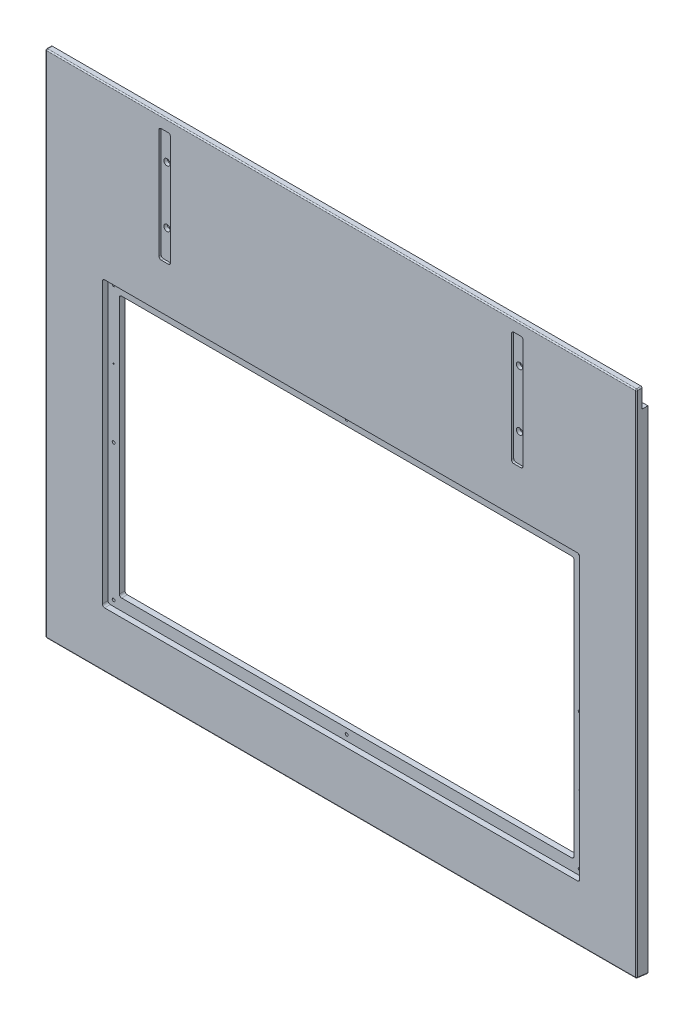
SolidWorks part; units mm, degrees
ref_plane "Front Plane" through (0, 0, 0) normal (0, 0, 1) x (1, 0, 0)
ref_plane "Top Plane" through (0, 0, 0) normal (0, 1, 0) x (1, 0, 0)
ref_plane "Right Plane" through (0, 0, 0) normal (1, 0, 0) x (0, 0, -1)
sketch "Sketch2" plane through (0, 0, 0) normal (0, 0, 1) x (1, 0, 0)
  line L1 (-260, -390) -> (260, -390)
  line L2 (-260, -390) -> (-260, 60)
  line L3 (-260, 60) -> (260, 60)
  line L4 (260, -390) -> (260, 60)
  line L5 (-260, -390) -> (260, 60) construction
  line L6 (-260, 60) -> (260, -390) construction
  point P0 (0, -165)
  dimension "D1" = 60
  dimension "D2" = 520
  dimension "D3" = 450
extrude "Boss-Extrude2" add sketch "Sketch2" against normal blind 10
ref_plane "Plane1" through (0, -215, 0) normal (0, 1, 0) x (1, 0, 0)
ref_axis "Axis1" through (0, -215, 0.5) along (0, 0, -1)
sketch "Sketch3" plane through (0, 0, 0) normal (0, 0, 1) x (1, 0, 0)
  line L1 (-160.2, 50.1) -> (-150, 50.1)
  line L2 (-160.2, 50.1) -> (-160.2, -50.1)
  line L3 (-160.2, -50.1) -> (-150, -50.1)
  line L4 (-150, 50.1) -> (-150, -50.1)
  line L5 (-160.2, 50.1) -> (-150, -50.1) construction
  line L6 (-160.2, -50.1) -> (-150, 50.1) construction
  line L7 (5.5, 0) -> (-5.5, 0) construction
  line L8 (0, -5.5) -> (0, 5.5) construction
  point P0 (-155.1, 0)
  dimension "D1" = 155.1
  dimension "D2" = 10.2
  dimension "D3" = 100.2
extrude "Cut-Extrude1" cut sketch "Sketch3" against normal blind 2
fillet "Fillet2" radius 2 4 edges at (-160.2, -50.1, -1) (-150, -50.1, -1) (-150, 50.1, -1) (-160.2, 50.1, -1)
hole_wizard "CBORE for M5 SHCS1" positions "Sketch5" profile "Sketch6" counterbore size "M5" standard "ANSI Metric" end condition through all
sketch "Sketch5" plane through (0, 0, -10) normal (0, 0, -1) x (-1, 0, 0)
  line L0 (5.5, 0) -> (-5.5, 0) construction
  line L2 (0, 5.5) -> (0, -5.5) construction
  point P0 (155.1, 25)
  point P3 (155.1, -25)
  dimension "D1" = 25
  dimension "D2" = 25
  dimension "D3" = 155.1
sketch "Sketch6" plane through (-155.1, 25, -10) normal (1, 0, 0) x (0, 1, 0)
  line L0 (0, 0) -> (0, 10)
  line L1 (0, 10) -> (2.75, 10)
  line L3 (2.75, 10) -> (2.75, 5)
  line L4 (2.75, 5) -> (5, 5)
  line L5 (5, 5) -> (5, 0)
  line L7 (5, 0) -> (0, 0)
  line L11 (0, -6.35) -> (0, 107.95) construction
  dimension "Thru Hole Dia." = 5.5
  dimension "Thru Hole Depth" = 10
  dimension "C'Bore Dia." = 10
  dimension "C'Bore Depth" = 5
mirror "Mirror8" about plane through (0, 0, 0) normal (1, 0, 0) of "CBORE for M5 SHCS1", "Fillet2", "Cut-Extrude1"
sketch "Sketch7" plane through (0, 0, 0) normal (0, 0, 1) x (1, 0, 0)
  line L1 (-200, -100) -> (200, -100)
  line L2 (-200, -100) -> (-200, -330)
  line L3 (-200, -330) -> (200, -330)
  line L4 (200, -100) -> (200, -330)
  line L5 (-200, -100) -> (200, -330) construction
  line L6 (-200, -330) -> (200, -100) construction
  point P0 (0, -215)
  dimension "D1" = 400
  dimension "D2" = 230
extrude "Cut-Extrude3" cut sketch "Sketch7" against normal through all
fillet "Fillet3" radius 2 4 edges at (200, -330, -5) (200, -100, -5) (-200, -330, -5) (-200, -100, -5)
sketch "Sketch9" plane through (0, 0, 0) normal (0, 0, 1) x (1, 0, 0)
  line L0 (-200, -102) -> (-200, -328) construction
  line L1 (-210, -90) -> (210, -90)
  line L2 (-210, -90) -> (-210, -340)
  line L3 (-210, -340) -> (210, -340)
  line L4 (210, -90) -> (210, -340)
  line L5 (-210, -90) -> (210, -340) construction
  line L6 (-210, -340) -> (210, -90) construction
  line L7 (-198, -330) -> (198, -330) construction
  point P0 (0, -215)
  dimension "D1" = 10
  dimension "D2" = 10
extrude "Cut-Extrude5" cut sketch "Sketch9" against normal blind 5
fillet "Fillet4" radius 2 4 edges at (210, -90, -2.5) (210, -340, -2.5) (-210, -340, -2.5) (-210, -90, -2.5)
hole_wizard "M3 Tapped Hole1" positions "Sketch13" profile "Sketch14" tap size "M3" standard "DIN" end condition through all
sketch "Sketch13" plane through (0, 0, -5) normal (0, 0, 1) x (1, 0, 0)
  line L0 (0, -5.5) -> (0, 5.5) construction
  line L1 (5.5, -215) -> (-5.5, -215) construction
  line L4 (-200, -328) -> (-200, -102) construction
  line L5 (-198, -100) -> (198, -100) construction
  line L6 (198, -330) -> (-198, -330) construction
  line L7 (200, -102) -> (200, -328) construction
  point P0 (-205, -95)
  point P2 (0, -95)
  point P4 (-205, -215)
  point P21 (205, -95)
  point P23 (205, -215)
  point P25 (205, -335)
  point P27 (0, -335)
  point P29 (-205, -335)
  dimension "D1" = 5
  dimension "D2" = 5
  dimension "D3" = 5
  dimension "D4" = 5
sketch "Sketch14" plane through (-205, -95, -5) normal (1, 0, 0) x (0, -1, 0)
  line L0 (0, 0) -> (0, 5)
  line L1 (0, 5) -> (1.25, 5)
  line L2 (1.25, 5) -> (1.25, 0)
  line L5 (1.25, 0) -> (0, 0)
  line L11 (0, -6.35) -> (0, 107.95) construction
  dimension "Thru Tap Drill Dia." = 2.5
  dimension "Thru Tap Drill Depth" = 5
cosmetic thread "Hole Thread1" parameters "D2"=3
cosmetic thread "Hole Thread2" parameters "D2"=3
cosmetic thread "Hole Thread3" parameters "D2"=3
cosmetic thread "Hole Thread4" parameters "D2"=3
cosmetic thread "Hole Thread5" parameters "D2"=3
cosmetic thread "Hole Thread6" parameters "D2"=3
cosmetic thread "Hole Thread7" parameters "D2"=3
cosmetic thread "Hole Thread8" parameters "D2"=3
sketch "Sketch12" plane through (0, 0, -10) normal (0, 0, -1) x (-1, 0, 0)
  line L0 (260, -390) -> (-260, -390) construction
  line L1 (10, -390) -> (-10, -390)
  line L2 (10, -390) -> (10, -386.5)
  line L3 (7.5, -384) -> (-7.5, -384)
  line L4 (-10, -390) -> (-10, -386.5)
  line L5 (10, -390) -> (-10, -384) construction
  line L6 (10, -384) -> (-10, -390) construction
  line L7 (0, 5.5) -> (0, -5.5) construction
  arc A0 (-7.5, -384) -> (-10, -386.5) centre (-7.5, -386.5) ccw
  arc A1 (10, -386.5) -> (7.5, -384) centre (7.5, -386.5) ccw
  point P0 (0, -387)
  dimension "D3" = 2.5
  dimension "D1" = 20
  dimension "D2" = 6
extrude "Cut-Extrude8" cut sketch "Sketch12" against normal blind 6
sketch "Sketch11" plane through (0, 0, 0) normal (1, 0, 0) x (0, 0, -1)
  line L0 (10, -390) -> (0, -388.6853)
  line L1 (10, 60) -> (5, 60)
  line L2 (10, 60) -> (10, 43)
  line L3 (10, 43) -> (5, 43)
  line L4 (5, 60) -> (5, 43)
  line L5 (0, 60) -> (0, -390) construction
  line L6 (0, -388.6853) -> (0, -390)
  line L7 (0, -390) -> (10, -390)
  dimension "D1" = 5
  dimension "D2" = 17
  dimension "D3" = 7.49
extrude "Cut-Extrude7" cut sketch "Sketch11" against normal through all both and the other way through all
fillet "Fillet1" radius 1 8 edges at (-260, 60, -2.5) (260, 60, -2.5) (260, -389.3426, -5) (-260, -389.3426, -5) (0, 60, 0) (-260, -164.3426, 0) (0, -388.6853, 0) (260, -164.3426, 0)
hole_wizard "M5x0.8 Tapped Hole1" positions "Sketch15" profile "Sketch16" tap size "M5x0.8" standard "ANSI Metric"
sketch "Sketch15" plane through (0, 0, -10) normal (0, 0, -1) x (-1, 0, 0)
  line L0 (0, 5.5) -> (0, -5.5) construction
  line L1 (259, 60) -> (-259, 60) construction
  point P0 (-215, 34)
  point P2 (-190, 34)
  point P4 (-12.5, 34)
  point P6 (12.5, 34)
  point P8 (190, 34)
  point P10 (215, 34)
  dimension "D1" = 12.5
  dimension "D2" = 12.5
  dimension "D3" = 25
  dimension "D4" = 25
  dimension "D5" = 190
  dimension "D6" = 190
  dimension "D7" = 26
sketch "Sketch16" plane through (215, 34, -10) normal (1, 0, 0) x (0, 1, 0)
  line L0 (0, 0) -> (0, 9.2618)
  line L1 (0, 9.2618) -> (2.1, 8)
  line L2 (2.1, 8) -> (2.1, 0)
  line L5 (2.1, 0) -> (0, 0)
  line L10 (0, 9.2618) -> (-2.1, 8) construction
  line L11 (0, -6.35) -> (0, 107.95) construction
  dimension "Tap Drill Dia." = 4.2
  dimension "Tap Drill Depth" = 8
  dimension "Drill Angle" = 118
cosmetic thread "Hole Thread9" parameters "D1"=6, "D2"=5
cosmetic thread "Hole Thread10" parameters "D1"=6, "D2"=5
cosmetic thread "Hole Thread11" parameters "D1"=6, "D2"=5
cosmetic thread "Hole Thread12" parameters "D1"=6, "D2"=5
cosmetic thread "Hole Thread13" parameters "D1"=6, "D2"=5
cosmetic thread "Hole Thread14" parameters "D1"=6, "D2"=5
sketch "Sketch17" plane through (0, 0, -10) normal (0, 0, -1) x (-1, 0, 0)
  line L0 (259, -390) -> (10, -390) construction
  line L1 (153.35, -390) -> (134.35, -390)
  line L2 (153.35, -390) -> (153.35, -363)
  line L3 (153.35, -363) -> (134.35, -363)
  line L4 (134.35, -390) -> (134.35, -363)
  line L5 (153.35, -390) -> (134.35, -363) construction
  line L6 (153.35, -363) -> (134.35, -390) construction
  line L7 (0, 5.5) -> (0, -5.5) construction
  point P0 (143.85, -376.5)
  dimension "D1" = 27
  dimension "D2" = 19
  dimension "D3" = 143.85
extrude "Cut-Extrude9" cut sketch "Sketch17" against normal blind 2
fillet "Fillet5" radius 2 2 edges at (-134.35, -363, -9) (-153.35, -363, -9)
hole_wizard "M4x0.7 Tapped Hole1" positions "Sketch18" profile "Sketch19" tap size "M4x0.7" standard "ANSI Metric"
sketch "Sketch18" plane through (0, 0, -8) normal (0, 0, -1) x (-1, 0, 0)
  line L0 (151.35, -363) -> (136.35, -363) construction
  line L1 (0, 5.5) -> (0, -5.5) construction
  point P0 (143.85, -385)
  point P2 (143.85, -370)
  dimension "D1" = 15
  dimension "D2" = 7
  dimension "D3" = 143.85
sketch "Sketch19" plane through (-143.85, -385, -8) normal (1, 0, 0) x (0, 1, 0)
  line L0 (0, 0) -> (0, 6.9914)
  line L1 (0, 6.9914) -> (1.65, 6)
  line L2 (1.65, 6) -> (1.65, 0)
  line L5 (1.65, 0) -> (0, 0)
  line L10 (0, 6.9914) -> (-1.65, 6) construction
  line L11 (0, -6.35) -> (0, 107.95) construction
  dimension "Tap Drill Dia." = 3.3
  dimension "Tap Drill Depth" = 6
  dimension "Drill Angle" = 118
cosmetic thread "Hole Thread15" parameters "D1"=5, "D2"=4
cosmetic thread "Hole Thread16" parameters "D1"=5, "D2"=4
mirror "Mirror10" about plane through (0, 0, 0) normal (1, 0, 0) of "M4x0.7 Tapped Hole1", "Fillet5", "Cut-Extrude9"
hole_wizard "Ø1.0mm Dowel Hole1" positions "Sketch20" profile "Sketch21" hole size "Ø1.0" standard "ANSI Metric"
sketch "Sketch20" plane through (0, 0, -5) normal (0, 0, 1) x (1, 0, 0)
  line L0 (5.5, -215) -> (-5.5, -215) construction
  line L1 (-200, -328) -> (-200, -102) construction
  line L2 (200, -102) -> (200, -328) construction
  point P0 (-205, -155)
  point P2 (205, -275)
  dimension "D1" = 60
  dimension "D2" = 60
  dimension "D3" = 5
  dimension "D4" = 5
sketch "Sketch21" plane through (-205, -155, -5) normal (1, 0, 0) x (0, -1, 0)
  line L0 (0, 0) -> (0, 4.3004)
  line L1 (0, 4.3004) -> (0.5, 4)
  line L2 (0.5, 4) -> (0.5, 0)
  line L5 (0.5, 0) -> (0, 0)
  line L10 (0, 4.3004) -> (-0.5, 4) construction
  line L11 (0, -6.35) -> (0, 107.95) construction
  dimension "Hole Dia." = 1
  dimension "Hole Depth" = 4
  dimension "Drill Angle" = 118
